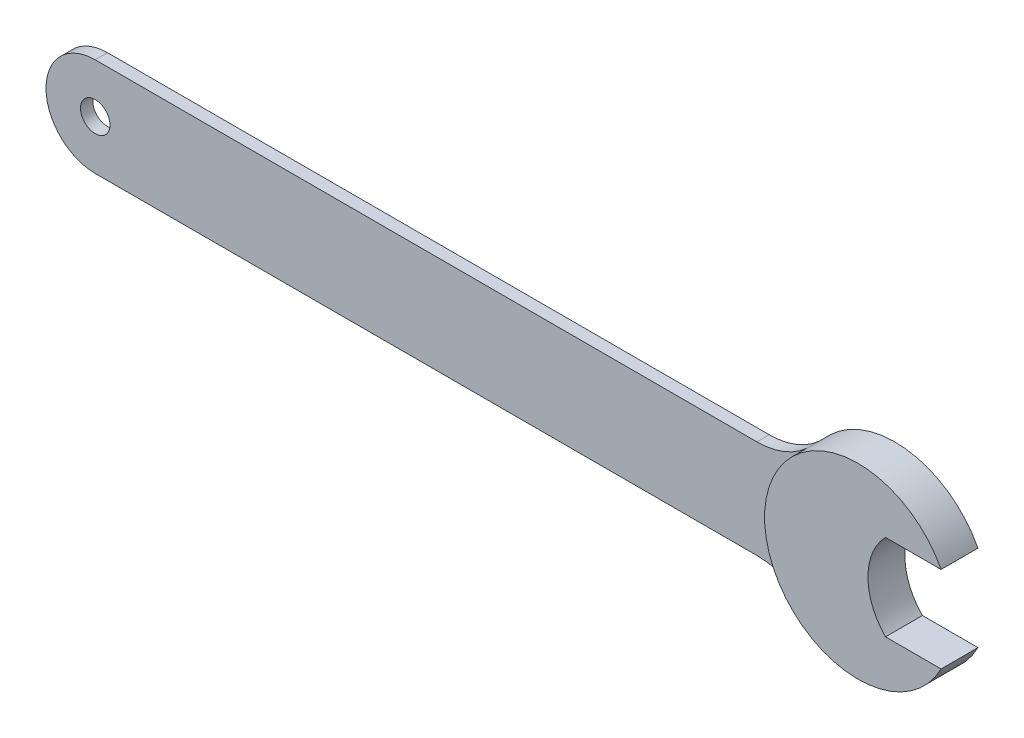
SolidWorks part; units mm, degrees
ref_plane "Front Plane" through (0, 0, 0) normal (0, 0, 1) x (1, 0, 0)
ref_plane "Top Plane" through (0, 0, 0) normal (0, 1, 0) x (1, 0, 0)
ref_plane "Right Plane" through (0, 0, 0) normal (1, 0, 0) x (0, 0, -1)
sketch "Sketch1" plane through (0, 0, 0) normal (0, 0, 1) x (1, 0, 0)
  line L0 (-5.7723, 0) -> (693.7723, 0) construction
  line L1 (0, 20) -> (268.9131, 20)
  line L2 (0, -20) -> (268.9131, -20)
  line L3 (326.1464, 17.5) -> (348.7305, 17.5)
  line L4 (348.7305, -17.5) -> (326.1464, -17.5)
  arc A0 (348.7305, 17.5) -> (348.7305, -17.5) centre (315, 0) ccw
  arc A1 (0, 20) -> (0, -20) centre (0, 0) ccw
  circle A2 centre (0, 0) radius 6
  arc A3 (268.9131, -20) -> (289.2456, -27.9412) centre (268.9131, -50) cw
  arc A4 (268.9131, 20) -> (289.2456, 27.9412) centre (268.9131, 50) ccw
  arc A5 (326.1464, 17.5) -> (326.1464, -17.5) centre (344, 0) ccw
  point P21 (349.4746, 0.7875)
  point P22 (0, 0)
  point P23 (0, 0)
  point P24 (0, 0)
  point P25 (0, 0)
  point P26 (348.7305, 17.5)
  point P27 (348.7305, -17.5)
  dimension "D1" = 315
  dimension "D2" = 12
  dimension "D3" = 40
  dimension "D4" = 76
  dimension "D5" = 30
  dimension "D6" = 30
  dimension "D7" = 25
  dimension "D8" = 35
  dimension "D9" = 29
extrude "Boss-Extrude1" add sketch "Sketch1" along normal mid plane 5 contours A2 A0 A4 L1 A1 L2 A3 region at (133.3701, 0, 0)
extrude "Boss-Extrude2" add sketch "Sketch1<3>" along normal mid plane 15 contours A0 L0 A5 L3 | L0 A0 L4 A5 region at (308.4554, 18.5499, 0) region at (308.4554, -18.5499, 0)
sketch "Sketch1<3>" plane through (0, 0, 0) normal (0, 0, 1) x (1, 0, 0) same geometry as "Sketch1"
